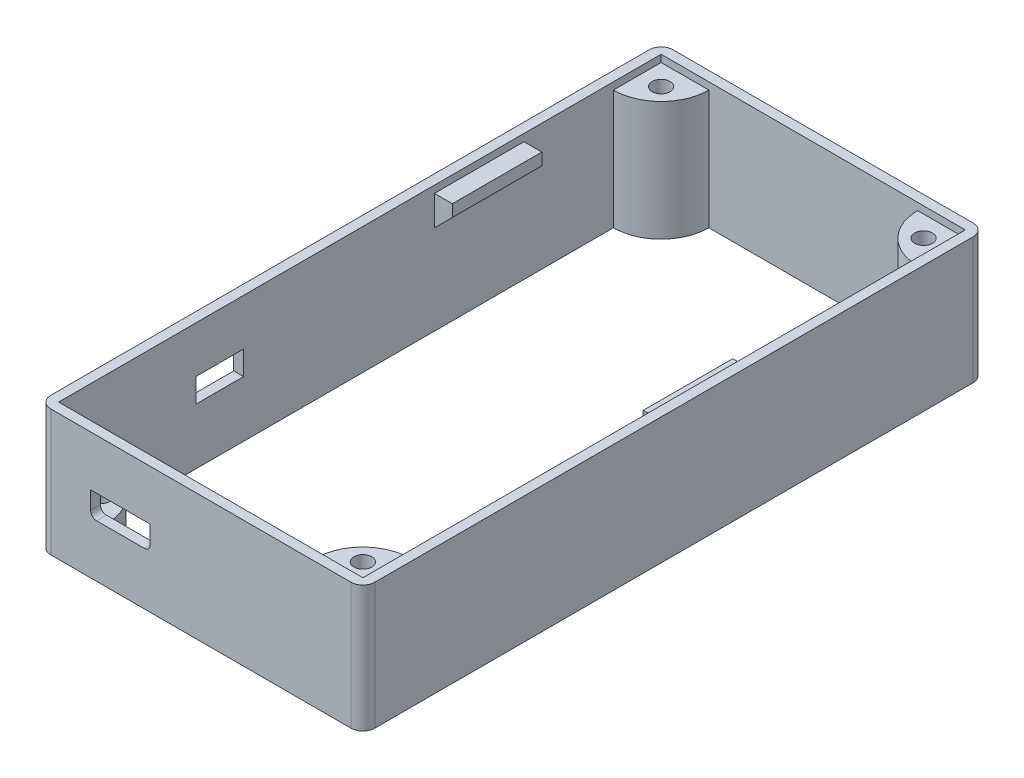
SolidWorks part; units mm, degrees
ref_plane "Přední rovina" through (0, 0, 0) normal (0, 0, 1) x (1, 0, 0)
ref_plane "Horní rovina" through (0, 0, 0) normal (0, 1, 0) x (1, 0, 0)
ref_plane "Pravá rovina" through (0, 0, 0) normal (1, 0, 0) x (0, 0, -1)
sketch "Skica1" plane through (0, 0, 0) normal (0, 1, 0) x (1, 0, 0)
  line L1 (0, 0) -> (51, 0)
  line L2 (0, 0) -> (0, 101)
  line L3 (0, 101) -> (51, 101)
  line L4 (51, 0) -> (51, 101)
  line L5 (-1.65, -1.65) -> (52.65, -1.65)
  line L6 (-1.65, -1.65) -> (-1.65, 102.65)
  line L7 (-1.65, 102.65) -> (52.65, 102.65)
  line L8 (52.65, -1.65) -> (52.65, 102.65)
  dimension "D1" = 51
  dimension "D2" = 101
  dimension "D3" = 1.65
  dimension "D4" = 1.65
  dimension "D5" = 1.65
  dimension "D6" = 1.65
extrude "Přidat vysunutím1" add sketch "Skica1" along normal blind 1.2
sketch "Skica2" plane through (0, 0, 0) normal (0, -1, 0) x (1, 0, 0)
  line L1 (-1.65, 1.65) -> (52.65, 1.65)
  line L2 (-1.65, 1.65) -> (-1.65, -102.65)
  line L3 (-1.65, -102.65) -> (52.65, -102.65)
  line L4 (52.65, 1.65) -> (52.65, -102.65)
  line L5 (0, 0) -> (51, 0)
  line L6 (0, 0) -> (0, -101)
  line L7 (0, -101) -> (51, -101)
  line L8 (51, 0) -> (51, -101)
  arc A0 (0, -8) -> (8, 0) centre (0, 0) ccw
  arc A1 (43, 0) -> (51, -8) centre (51, 0) ccw
  arc A2 (51, -93) -> (43, -101) centre (51, -101) ccw
  arc A3 (8, -101) -> (0, -93) centre (0, -101) ccw
  line M9 (-1.65, 1.65) -> (-1.65, -102.65)
  line M10 (-1.65, -102.65) -> (52.65, -102.65)
  line M11 (52.65, -102.65) -> (52.65, 1.65)
  line M12 (52.65, 1.65) -> (-1.65, 1.65)
  line M13 (51, -101) -> (0, -101)
  line M14 (0, -101) -> (0, 0)
  line M15 (0, 0) -> (51, 0)
  line M16 (51, 0) -> (51, -101)
  dimension "D1" = 16
  dimension "D2" = 16
  dimension "D3" = 16
  dimension "D4" = 16
extrude "Přidat vysunutím2" add sketch "Skica2" along normal blind 20 contours L8 L7 L6 L5 M12 M9 M10 M11 M16 M13 M14 M15 | L6 A0 M15 | A3 M13 M14 | A2 M16 M13 | A1 M15 M16 region at (25.5, 0, 0.4741) region at (3.3953, 0, -3.3953) region at (47.6047, 0, -3.3953) region at (3.3953, 0, -97.6047) region at (47.6047, 0, -97.6047)
sketch "Skica3" plane through (0, 0, 0) normal (0, 1, 0) x (1, 0, 0)
  line L0 (8, 101) -> (43, 101) construction
  line L1 (51, 93) -> (51, 8) construction
  circle A0 centre (3.5, 97.5) radius 1.5
  circle A1 centre (47.5, 97.5) radius 1.5
  circle A3 centre (47.5, 3.5) radius 1.5
  point P8 (25.5, 101)
  point P11 (51, 50.5)
  dimension "D1" = 3
  dimension "D2" = 3
  dimension "D4" = 3
  dimension "D5" = 44
  dimension "D6" = 94
  dimension "D7" = 22
  dimension "D8" = 47
extrude "Odebrat vysunutím1" cut sketch "Skica3" against normal through all
sketch "Skica5" plane through (0, 0, 0) normal (1, 0, 0) x (0, 0, -1)
  line L0 (0, 1.2) -> (0, 0) construction
  line L1 (23, -10.6) -> (31, -10.6)
  line L2 (23, -10.6) -> (23, -6.6)
  line L3 (23, -6.6) -> (31, -6.6)
  line L4 (31, -10.6) -> (31, -6.6)
  line L6 (102.65, 1.2) -> (-1.65, 1.2) construction
  dimension "D1" = 23
  dimension "D2" = 8
  dimension "D3" = 11.8
  dimension "D4" = 4
extrude "Odebrat vysunutím2" cut sketch "Skica5" against normal blind 2
sketch "Skica6" plane through (0, 0, 0) normal (0, 0, -1) x (-1, 0, 0)
  line L0 (0, 1.2) -> (0, 0) construction
  line L1 (-7, -11.2) -> (-17, -11.2)
  line L2 (-7, -11.2) -> (-7, -7.2)
  line L3 (-7, -7.2) -> (-17, -7.2)
  line L4 (-17, -11.2) -> (-17, -7.2)
  line L5 (1.65, 1.2) -> (-52.65, 1.2) construction
  point P6 (0, 0.6)
  dimension "D1" = 10
  dimension "D2" = 7
  dimension "D3" = 4
  dimension "D4" = 8.4
extrude "Odebrat vysunutím3" cut sketch "Skica6" against normal mid plane 10
sketch "Skica9" plane through (51, 0, 0) normal (-1, 0, 0) x (0, 0, 1)
  line L0 (0, 0) -> (-8, 0) construction
  line L1 (-64, 0) -> (-49, 0)
  line L2 (-64, 0) -> (-64, -5)
  line L3 (-64, -5) -> (-49, -5)
  line L4 (-49, 0) -> (-49, -5)
  line L5 (-101, 1.2) -> (-101, 0) construction
  dimension "D1" = 15
  dimension "D2" = 37
  dimension "D3" = 5
extrude "Přidat vysunutím4" add sketch "Skica9" along normal blind 2
chamfer "Zkosení1" distance 2 1 edges at (49, -5, -56.5)
sketch "Skica10" plane through (0, 0, 0) normal (1, 0, 0) x (0, 0, -1)
  line L0 (101, 0) -> (93, 0) construction
  line L1 (78, 0) -> (63, 0)
  line L2 (78, 0) -> (78, -5)
  line L3 (78, -5) -> (63, -5)
  line L4 (63, 0) -> (63, -5)
  line L5 (101, 1.2) -> (101, 0) construction
  dimension "D1" = 15
  dimension "D2" = 5
  dimension "D3" = 38
extrude "Přidat vysunutím5" add sketch "Skica10" along normal blind 3
chamfer "Zkosení2" distance 3 1 edges at (3, -5, -70.5)
fillet "Zaoblit2" radius 1 2 edges at (7, -11.2, -1.1115) (17, -11.2, 0.825)
fillet "Zaoblit3" radius 2 4 edges at (-1.65, -9.4, -102.65) (-1.65, -9.4, 1.65) (52.65, -9.4, 1.65) (52.65, -9.4, -102.65)
sketch "Skica11" plane through (0, 0, 0) normal (0, 1, 0) x (1, 0, 0)
  line L0 (0, 8) -> (0, 0)
  line L1 (0, 0) -> (8, 0)
  arc A0 (8, 0) -> (0, 8) centre (0, 0) ccw
extrude "Odebrat vysunutím5" cut sketch "Skica11" against normal blind 12.5
sketch "Skica12" plane through (0, -20, 0) normal (0, -1, 0) x (1, 0, 0)
  line L0 (47.5, -3.5) -> (3.5, -3.5) construction
  line L1 (3.5, -3.5) -> (3.5, -97.5) construction
  circle A0 centre (3.5, -3.5) radius 1.5
  dimension "D1" = 3
extrude "Odebrat vysunutím6" cut sketch "Skica12" against normal through all
